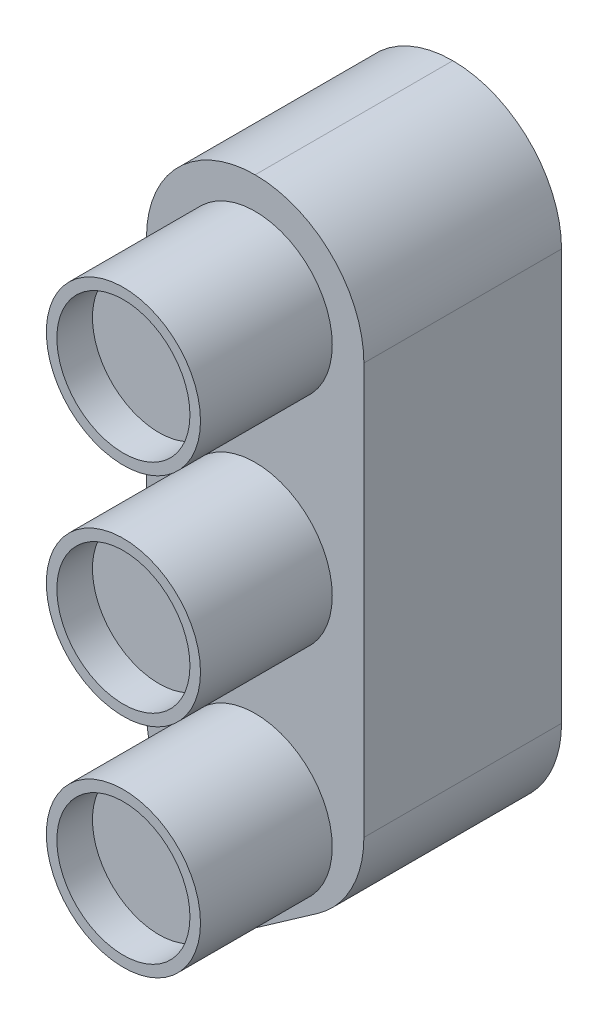
SolidWorks part; units mm, degrees
ref_plane "Ebene vorne" through (0, 0, 0) normal (0, 0, 1) x (1, 0, 0)
ref_plane "Ebene oben" through (0, 0, 0) normal (0, 1, 0) x (1, 0, 0)
ref_plane "Ebene rechts" through (0, 0, 0) normal (1, 0, 0) x (0, 0, -1)
sketch "Sketch1" plane through (0, 0, 0) normal (0, 0, 1) x (1, 0, 0)
  line L1 (0, 0) -> (-165, 0) construction
  line L2 (0, 0) -> (0, 165) construction
  line L3 (0, 165) -> (-165, 165) construction
  line L4 (-165, 0) -> (-165, 165) construction
  line L13 (-99, 165) -> (-82.5, 165)
  line L14 (-99, 165) -> (-99, 115.5)
  line L15 (-99, 115.5) -> (-82.5, 115.5)
  line L16 (-82.5, 165) -> (-82.5, 115.5)
  dimension "D1" = 165
  dimension "D2" = 165
  dimension "D8" = 49.5
  dimension "D9" = 16.5
extrude "Boss-Extrude1" add sketch "Sketch1" along normal blind 25
sketch "Sketch2" plane through (0, 0, 25) normal (0, 0, 1) x (1, 0, 0)
  line L0 (-99, 140.25) -> (-82.5, 140.25) construction
  line L1 (-99, 165) -> (-99, 115.5) construction
  line L2 (-82.5, 115.5) -> (-82.5, 165) construction
  line L4 (-99, 165) -> (-82.5, 165)
  line L5 (-99, 165) -> (-99, 115.5)
  line L6 (-99, 115.5) -> (-82.5, 115.5)
  line L7 (-82.5, 165) -> (-82.5, 115.5)
  circle A0 centre (-90.75, 156.75) radius 5.85
  circle A1 centre (-90.75, 156.75) radius 5.05
  circle A2 centre (-90.75, 140.25) radius 5.85
  circle A3 centre (-90.75, 140.25) radius 5.05
  circle A4 centre (-90.75, 123.75) radius 5.85
  circle A5 centre (-90.75, 123.75) radius 5.05
  point P9 (-90.75, 140.25)
  line M6 (-99, 165) -> (-99, 115.5)
  line M7 (-99, 115.5) -> (-82.5, 115.5)
  line M8 (-82.5, 115.5) -> (-82.5, 165)
  line M9 (-82.5, 165) -> (-99, 165)
  dimension "D1" = 16.5
  dimension "D2" = 11.7
  dimension "D3" = 10.1
  dimension "D4" = 11.7
  dimension "D5" = 10.1
extrude "Cut-Extrude1" cut sketch "Sketch2" against normal blind 10 contours L0 A2 L7 A0 M6 M9 | L0 L5 A2 A4 M7 M8 | L0 A3 | A3 L0 | A5 | A1 region at (-90.75, 138.1067, 25) region at (-90.75, 142.3933, 25) region at (-90.75, 146.3975, 25) region at (-83.7, 139.9525, 25) region at (-90.75, 156.75, 25) region at (-90.75, 123.75, 25)
fillet "Fillet5" radius 8.25 2 edges at (-82.5, 165, 7.5) (-99, 165, 7.5)
chamfer "Chamfer1" distance 8.25 angle 35 2 edges at (-99, 115.5, 7.5) (-82.5, 115.5, 7.5) first distance on face at (-90.75, 115.5, 7.5)
fillet "Fillet6" radius 8.25 2 edges at (-82.5, 121.2767, 7.5) (-99, 121.2767, 7.5)
sketch "Sketch4" plane through (0, 0, 15) normal (0, 0, 1) x (1, 0, 0)
  circle A0 centre (-90.75, 156.75) radius 5.1
  circle A1 centre (-90.75, 140.25) radius 5.1
  circle A2 centre (-90.75, 123.75) radius 5.1
  dimension "D1" = 10.2
  dimension "D2" = 10.2
  dimension "D3" = 10.2
extrude "Boss-Extrude2" add sketch "Sketch4" along normal blind 7.3
sketch "Skizze2" plane through (0, 0, 0) normal (0, 0, -1) x (-1, 0, 0)
  line L8 (84.5, 156.75) -> (84.5, 125.5714)
  line L9 (87.1651, 120.4517) -> (90.75, 117.9415)
  line L10 (90.75, 117.9415) -> (94.3349, 120.4517)
  line L11 (97, 125.5714) -> (97, 156.75)
  line L12 (84.5, 156.75) -> (84.5, 125.5714)
  line L13 (87.1651, 120.4517) -> (90.75, 117.9415)
  line L14 (90.75, 117.9415) -> (94.3349, 120.4517)
  line L15 (97, 125.5714) -> (97, 156.75)
  arc A8 (84.5, 125.5714) -> (87.1651, 120.4517) centre (90.75, 125.5714) ccw
  arc A9 (94.3349, 120.4517) -> (97, 125.5714) centre (90.75, 125.5714) ccw
  arc A10 (97, 156.75) -> (90.75, 163) centre (90.75, 156.75) ccw
  arc A11 (90.75, 163) -> (84.5, 156.75) centre (90.75, 156.75) ccw
  arc A12 (84.5, 125.5714) -> (87.1651, 120.4517) centre (90.75, 125.5714) ccw
  arc A13 (94.3349, 120.4517) -> (97, 125.5714) centre (90.75, 125.5714) ccw
  arc A14 (97, 156.75) -> (90.75, 163) centre (90.75, 156.75) ccw
  arc A15 (90.75, 163) -> (84.5, 156.75) centre (90.75, 156.75) ccw
  dimension "D1" = 2
extrude "Schnitt-Linear austragen1" cut sketch "Skizze2" against normal blind 9
